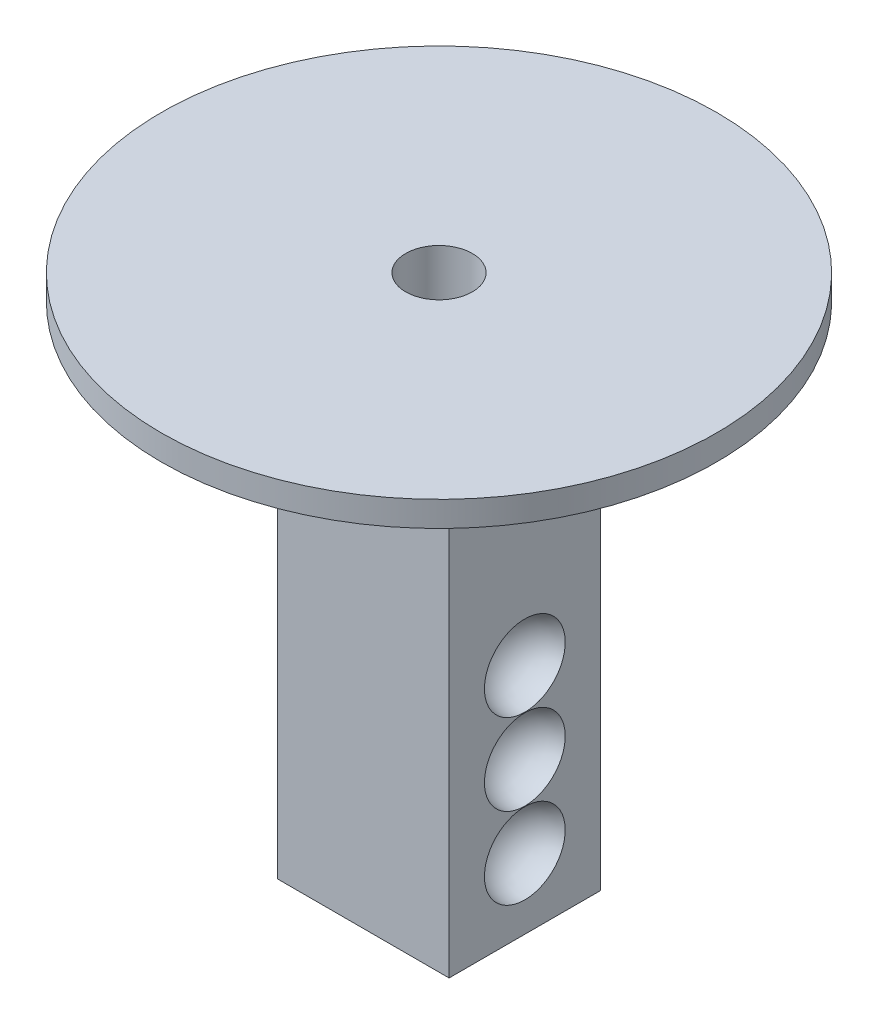
SolidWorks part; units mm, degrees
ref_plane "前视基准面" through (0, 0, 0) normal (0, 0, 1) x (1, 0, 0)
ref_plane "上视基准面" through (0, 0, 0) normal (0, 1, 0) x (1, 0, 0)
ref_plane "右视基准面" through (0, 0, 0) normal (1, 0, 0) x (0, 0, -1)
other "Configuration Table"
sketch "草图5" plane through (0, 0, 0) normal (0, 0, 1) x (1, 0, 0)
  line L1 (-17, 70) -> (0, 70)
  line L2 (-17, 70) -> (-17, -30)
  line L3 (-17, -30) -> (0, -30)
  line L4 (0, 70) -> (0, -30)
  dimension "D1" = 100
  dimension "D2" = 30
  dimension "D3" = 17
extrude "凸台-拉伸1" add sketch "草图5" along normal blind 15 and the other way blind 15
sketch "草图7" plane through (0, 0, 0) normal (0, 0, 1) x (1, 0, 0)
  line L0 (-17, -30) -> (0, -30) construction
  line L2 (-17, 70) -> (-17, -30) construction
  line L4 (-17, 8) -> (-17, -8)
  arc A1 (-17, -8) -> (-17, 8) centre (-17, 0) ccw
  dimension "D1" = 0
  dimension "D2" = 8
  dimension "D3" = 30
revolve "切除-旋转1" cut sketch "草图7" angle 360 about L4
pattern_linear "阵列(线性)1" count 2 spacing 16.1 along (0, 1, 0) count 2 spacing 16.1 along (0, -1, 0) of "切除-旋转1" pattern seed only yes
mirror "镜向2" about plane through (0, 0, 0) normal (1, 0, 0) of "凸台-拉伸1"
mirror "镜向3" about plane through (0, 0, 0) normal (1, 0, 0) of "切除-旋转1"
mirror "镜向4" about plane through (0, 0, 0) normal (1, 0, 0) of "阵列(线性)1"
sketch "草图9" plane through (0, 0, 0) normal (0, 0, 1) x (1, 0, 0)
  line L0 (17, 70) -> (-17, 70) construction
  line L1 (0, 70) -> (55, 70)
  line L2 (0, 70) -> (0, 75)
  line L3 (0, 75) -> (55, 75)
  line L4 (55, 70) -> (55, 75)
  dimension "D1" = 55
  dimension "D2" = 5
revolve "旋转1" add sketch "草图9" angle 360 about L2
sketch "草图12" plane through (0, 0, 0) normal (0, 1, 0) x (1, 0, 0)
  circle A0 centre (0, 0) radius 6.6
  dimension "D1" = 13.2
extrude "切除-拉伸1" cut sketch "草图12" against normal through all and the other way through all
sketch "草图15" plane through (0, 0, 0) normal (0, 1, 0) x (1, 0, 0)
  circle A0 centre (0, 0) radius 8
  dimension "D1" = 16
extrude "切除-拉伸4" cut sketch "草图15" against normal through all
